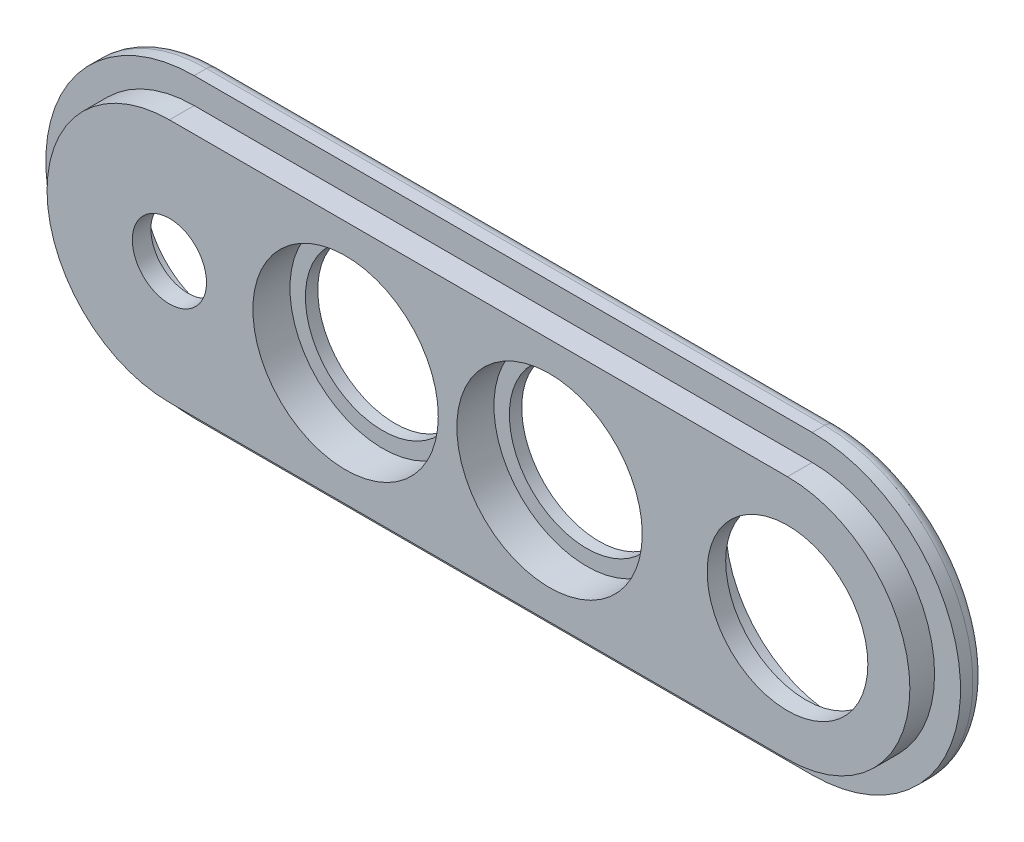
SolidWorks part; units mm, degrees
ref_plane "Спереди" through (0, 0, 0) normal (0, 0, 1) x (1, 0, 0)
ref_plane "Сверху" through (0, 0, 0) normal (0, 1, 0) x (1, 0, 0)
ref_plane "Справа" through (0, 0, 0) normal (1, 0, 0) x (0, 0, -1)
other "Configuration Table"
sketch "Эскиз1" plane through (0, 0, 0) normal (0, 0, 1) x (1, 0, 0)
  line L1 (0, 0) -> (50, 0)
  line L3 (0, -24) -> (50, -24)
  arc A0 (0, 0) -> (0, -24) centre (0, -12) ccw
  arc A1 (50, -24) -> (50, 0) centre (50, -12) ccw
  dimension "D1" = 24
  dimension "D2" = 50
extrude "Бобышка-Вытянуть1" add sketch "Эскиз1" along normal blind 4
sketch "Эскиз2" plane through (0, 0, 4) normal (0, 0, 1) x (1, 0, 0)
  line L0 (0, -12) -> (50, -12) construction
  line L1 (0, -2.1) -> (50, -2.1)
  line L2 (0, -21.9) -> (50, -21.9)
  line L3 (0, -12) -> (50, -12) construction
  line L4 (0, 0.0123) -> (50, 0.0123)
  line L5 (0, -24.0123) -> (50, -24.0123)
  arc A0 (0, -2.1) -> (0, -21.9) centre (0, -12) ccw
  arc A1 (50, -21.9) -> (50, -2.1) centre (50, -12) ccw
  arc A2 (0, 0.0123) -> (0, -24.0123) centre (0, -12) ccw
  arc A3 (50, -24.0123) -> (50, 0.0123) centre (50, -12) ccw
  point P4 (25, -12)
  point P11 (25, -12)
  dimension "D1" = 19.8
extrude "Вырез-Вытянуть1" cut sketch "Эскиз2" against normal blind 2
sketch "Эскиз3" plane through (0, 0, 4) normal (0, 0, 1) x (1, 0, 0)
  circle A0 centre (0, -12) radius 3
  circle A1 centre (50, -12) radius 6.5
  circle A2 centre (14.25, -12) radius 6.25
  circle A3 centre (30.75, -12) radius 6.25
  dimension "D1" = 6
  dimension "D2" = 13
  dimension "D3" = 12.5
  dimension "D5" = 12.5
  dimension "D4" = 14.25
  dimension "D6" = 16.5
  dimension "D7" = 50
extrude "Вырез-Вытянуть2" cut sketch "Эскиз3" against normal through all
sketch "Эскиз4" plane through (0, 0, 0) normal (0, 0, -1) x (-1, 0, 0)
  circle A0 centre (0, -12) radius 6
  circle A1 centre (-50, -12) radius 9
  dimension "D1" = 18
  dimension "D2" = 12
extrude "Вырез-Вытянуть3" cut sketch "Эскиз4" against normal blind 2.5
sketch "Эскиз5" plane through (0, 0, 0) normal (0, 0, -1) x (-1, 0, 0)
  circle A0 centre (-40, -4) radius 1.55
  circle A1 centre (-7, -4) radius 1.55
  circle A2 centre (-7, -20) radius 1.55
  circle A3 centre (-40, -20) radius 1.55
  circle A4 centre (-50, -12) radius 9 construction
  circle A5 centre (0, -12) radius 6 construction
  dimension "D1" = 3.1
  dimension "D2" = 8
  dimension "D3" = 8
  dimension "D4" = 10
  dimension "D5" = 7
extrude "Вырез-Вытянуть4" [suppressed] cut sketch "Эскиз5" against normal through all
sketch "Эскиз6" [suppressed] plane through (0, 0, 0) normal (0, 0, -1) x (-1, 0, 0)
  circle A0 centre (-40, -4) radius 3.2
  circle A1 centre (-7, -4) radius 3.2
  circle A2 centre (-7, -20) radius 3.2
  circle A3 centre (-40, -20) radius 3.2
  dimension "D1" = 6.4
extrude "Вырез-Вытянуть5" [suppressed] cut sketch "Эскиз6" against normal blind 2.5
fillet "Скругление1" radius 1 4 edges at (62, -12, 0) (25, -24, 0) (-12, -12, 0) (25, 0, 0)
sketch "Эскиз7" plane through (0, 0, 4) normal (0, 0, 1) x (1, 0, 0)
  circle A0 centre (30.75, -12) radius 7.5
  circle A1 centre (14.25, -12) radius 7.5
  dimension "D1" = 15
  dimension "D2" = 15
extrude "Вырез-Вытянуть6" cut sketch "Эскиз7" against normal blind 3
fillet "Скругление2" [suppressed] radius 1
